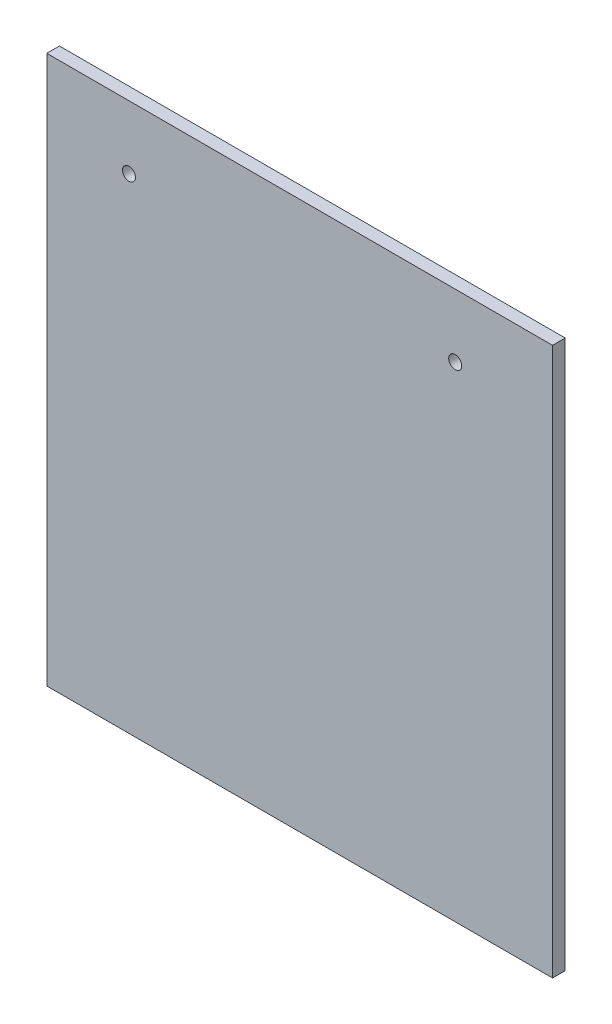
SolidWorks part; units mm, degrees
ref_plane "前视基准面" through (0, 0, 0) normal (0, 0, 1) x (1, 0, 0)
ref_plane "上视基准面" through (0, 0, 0) normal (0, 1, 0) x (1, 0, 0)
ref_plane "右视基准面" through (0, 0, 0) normal (1, 0, 0) x (0, 0, -1)
other "Configuration Table"
sketch "草图1" plane through (0, 0, 0) normal (0, 0, 1) x (1, 0, 0)
  line L1 (60, -65) -> (-60, -65)
  line L2 (60, -65) -> (60, 65)
  line L3 (60, 65) -> (-60, 65)
  line L4 (-60, -65) -> (-60, 65)
  line L5 (60, -65) -> (-60, 65) construction
  line L6 (60, 65) -> (-60, -65) construction
  point P0 (0, 0)
  dimension "D1" = 120
  dimension "D2" = 130
extrude "凸台-拉伸1" add sketch "草图1" along normal blind 3
sketch "草图5" plane through (0, 0, 3) normal (0, 0, 1) x (1, 0, 0)
  line L0 (0, 0) -> (0, 65) construction
  line L1 (60, 65) -> (-60, 65) construction
  circle A0 centre (36.9, 50) radius 1.55
extrude "切除-拉伸3" cut sketch "草图5" against normal through all contours A0
sketch "草图6" plane through (0, 0, 3) normal (0, 0, 1) x (1, 0, 0)
  circle A0 centre (-40.5, 50) radius 1.55
extrude "切除-拉伸4" cut sketch "草图6" against normal through all contours A0
